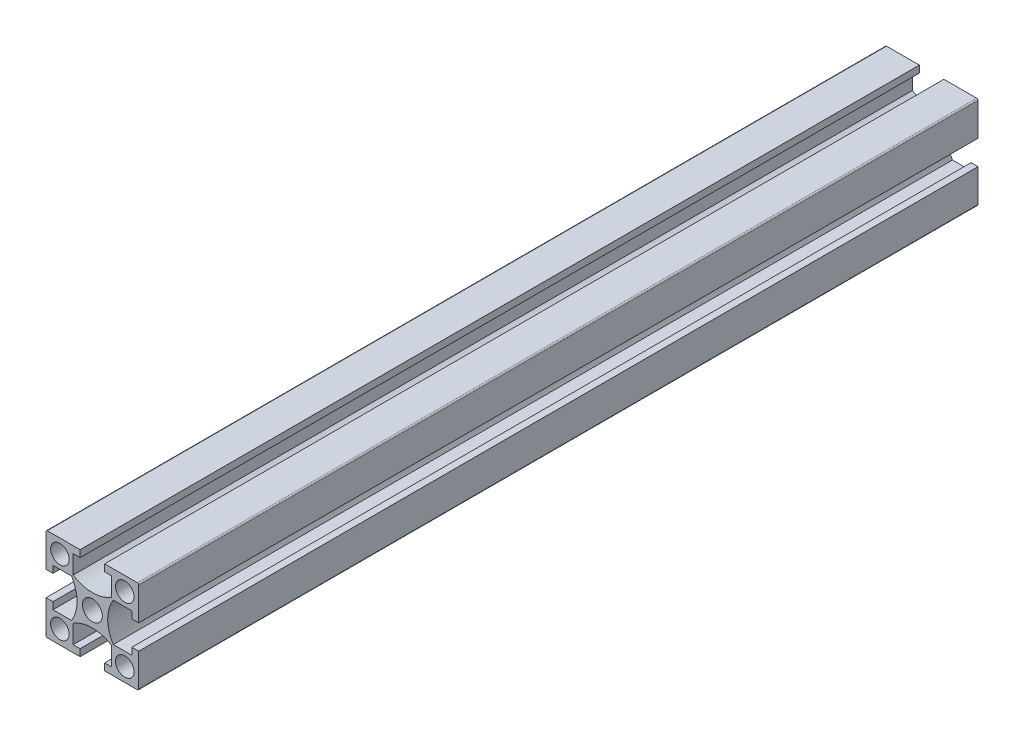
SolidWorks part; units mm, degrees
ref_plane "정면" through (0, 0, 0) normal (0, 0, 1) x (1, 0, 0)
ref_plane "윗면" through (0, 0, 0) normal (0, 1, 0) x (1, 0, 0)
ref_plane "우측면" through (0, 0, 0) normal (1, 0, 0) x (0, 0, -1)
sketch "스케치1" plane through (0, 0, 0) normal (0, 0, 1) x (1, 0, 0)
  line L0 (0, 32.0265) -> (0, -31.6588) construction
  line L1 (-10, 10) -> (-10, -10)
  line L2 (-10, 10) -> (10, 10)
  line L3 (-10, 2.65) -> (-8.5, 2.65)
  line L4 (13.6618, 0) -> (-11.6993, 0) construction
  line L5 (-8.5, 2.65) -> (-8.5, 4.15)
  line L6 (-8.5, 4.15) -> (-4.5032, 4.15)
  line L7 (-10, -2.65) -> (-8.5, -2.65)
  line L8 (-8.5, -2.65) -> (-8.5, -4.15)
  line L9 (-8.5, -4.15) -> (-4.5032, -4.15)
  line L10 (-10, -10) -> (10, -10)
  line L11 (10, 10) -> (10, -10)
  circle A0 centre (-7, 7) radius 2
  circle A1 centre (-7, -7) radius 2
  arc A2 (-4.5032, 4.15) -> (-4.5032, -4.15) centre (-11.0587, 0) cw
  circle A3 centre (0, 0) radius 2.15
  circle A4 centre (7, 7) radius 2
  circle A5 centre (7, -7) radius 2
  point P21 (-10, 0)
  point P23 (-3.3, 0)
  point P31 (0, -10)
  point P32 (0, 10)
  dimension "D3" = 4
  dimension "D9" = 6.7
  dimension "D10" = 4.3
  dimension "D11" = 7.7587
  dimension "D1" = 20
  dimension "D2" = 20
  dimension "D4" = 14
  dimension "D5" = 14
  dimension "D6" = 5.3
  dimension "D7" = 8.3
  dimension "D8" = 1.5
extrude "보스-돌출1" add sketch "스케치1" along normal blind 181 contours A0 | A4 | A3 | A5 | A1 | A2 L6 L5 L3 L1 L7 L8 L9 | L2 L11 L10 L1 region at (-6.6069, 0, 0) region at (-7, 7, 0) region at (-7, -7, 0) region at (0, 0, 0) region at (7, 7, 0) region at (7, -7, 0)
extrude "컷-돌출1" cut sketch "스케치1<3>" along normal up to next contours A2 L6 L5 L3 L1 L7 L8 L9 region at (-6.6069, 0, 0)
sketch "스케치1<3>" plane through (0, 0, 0) normal (0, 0, 1) x (1, 0, 0) same geometry as "스케치1"
pattern_circular "원형 패턴1" count 4 over 360 about axis through (0, 0, 181) along (0, 0, -1) of "컷-돌출1" reverse direction yes
fillet "필렛1" radius 0.3 4 edges at (10, -10, 90.5) (-10, -10, 90.5) (-10, 10, 90.5) (10, 10, 90.5)
